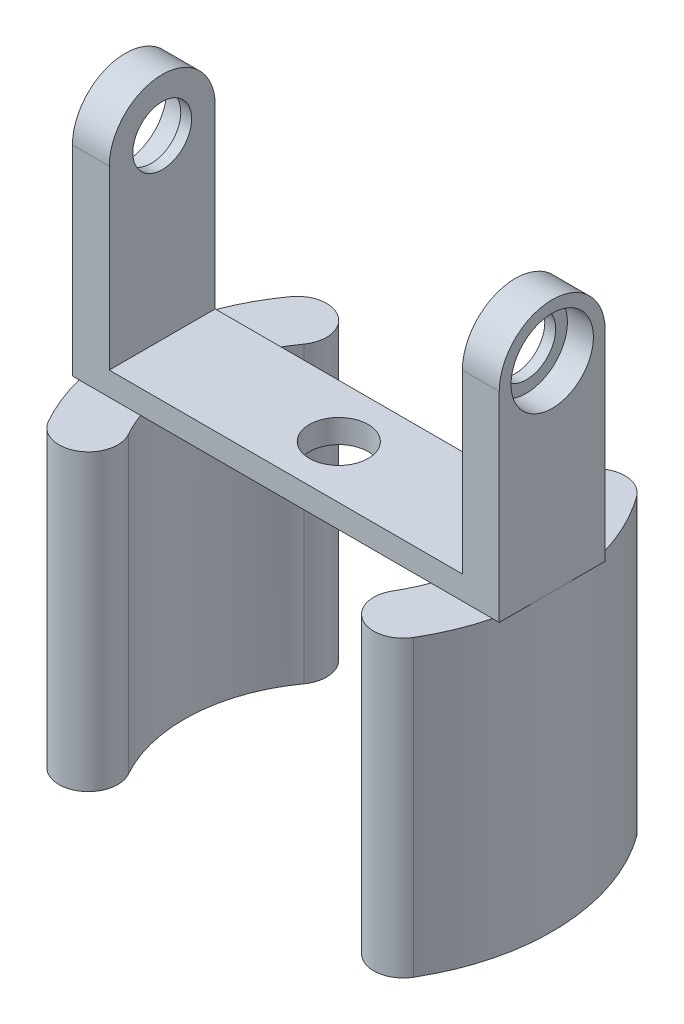
SolidWorks part; units mm, degrees
ref_plane "Front" through (0, 0, 0) normal (0, 0, 1) x (1, 0, 0)
ref_plane "Top" through (0, 0, 0) normal (0, 1, 0) x (1, 0, 0)
ref_plane "Right" through (0, 0, 0) normal (1, 0, 0) x (0, 0, -1)
sketch "Sketch1" plane through (0, 0, 0) normal (1, 0, 0) x (0, 0, -1)
  circle A0 centre (0, 0) radius 9
  circle A1 centre (0, 0) radius 5
  dimension "D1" = 10
  dimension "D2" = 18
extrude "Boss-Extrude1" add sketch "Sketch1" along normal blind 6.26
sketch "Sketch3" plane through (0, 0, 0) normal (-1, 0, 0) x (0, 0, 1)
  line L0 (-9, 0) -> (-9, -30)
  line L1 (-9, -30) -> (9, -30)
  line L2 (9, -30) -> (9, 0)
  line L3 (-9, 0) -> (9, 0) construction
  line L5 (-9, 0) -> (-5, 0)
  line L6 (5, 0) -> (9, 0)
  circle A0 centre (0, 0) radius 9 construction
  arc A1 (-5, 0) -> (5, 0) centre (0, 0) ccw
  circle A2 centre (0, 0) radius 5 construction
  point P10 (-9, 0)
  dimension "D1" = 30
extrude "Boss-Extrude2" add sketch "Sketch3" against normal up to surface (6.26 mm away) up to face at (6.26, 0, -9)
sketch "Sketch2" plane through (6.26, 0, 0) normal (1, 0, 0) x (0, 0, -1)
  circle A0 centre (0, 0) radius 7
  dimension "D1" = 14
extrude "Cut-Extrude1" cut sketch "Sketch2" against normal blind 4.41
sketch "Sketch4" plane through (0, -30, 0) normal (0, -1, 0) x (1, 0, 0)
  line L0 (6.26, -9) -> (6.26, 9) construction
  line L1 (6.26, 9) -> (-30, 9)
  line L2 (6.26, 9) -> (6.26, -9)
  line L3 (6.26, -9) -> (-30, -9)
  line L4 (-30, 9) -> (-30, -9)
  point P6 (6.26, 0)
  point P7 (6.26, 0)
  dimension "D1" = 36.26
  dimension "D2" = 18
extrude "Boss-Extrude3" add sketch "Sketch4" along normal blind 4
ref_plane "Plane1" through (-30, 0, 0) normal (-1, 0, 0) x (0, 0, 1)
mirror "Mirror2" about plane through (-30, -34, 9) normal (1, 0, 0) of bodies 104
sketch "Sketch5" plane through (0, -30, 0) normal (0, 1, 0) x (1, 0, 0)
  line L0 (-60, 9) -> (0, 9) construction
  line L1 (-30, 9) -> (-30, -9) construction
  line L2 (0, -9) -> (-60, -9) construction
  circle A0 centre (-30, 0) radius 5
  point P0 (-30, 9)
  dimension "D1" = 10
extrude "Cut-Extrude2" cut sketch "Sketch5" against normal through all
sketch "Sketch6" plane through (0, -34, 0) normal (0, -1, 0) x (1, 0, 0)
  line L0 (-0.5857, -21.2035) -> (-59.4143, -21.2035) construction
  line L1 (1.1847, 18.5014) -> (-61.6387, 17.7139) construction
  line L2 (6.26, -9) -> (6.26, 9) construction
  arc A0 (1.1847, 18.5014) -> (-0.5857, -21.2035) centre (-30, 0) cw
  arc A1 (-61.6387, 17.7139) -> (-59.4143, -21.2035) centre (-30, 0) ccw
  arc A2 (-7.4156, 13.399) -> (-8.6978, -15.3558) centre (-30, 0) cw
  arc A3 (1.1847, 18.5014) -> (-7.4156, 13.399) centre (-3.1154, 15.9502) ccw
  arc A4 (-0.5857, -21.2035) -> (-8.6978, -15.3558) centre (-4.6417, -18.2796) cw
  arc A5 (-52.9132, 12.8287) -> (-51.3022, -15.3558) centre (-30, 0) ccw
  arc A6 (-61.6387, 17.7139) -> (-52.9132, 12.8287) centre (-57.2759, 15.2713) cw
  arc A7 (-59.4143, -21.2035) -> (-51.3022, -15.3558) centre (-55.3583, -18.2796) ccw
  dimension "D1" = 10
  dimension "D2" = 10
extrude "Boss-Extrude4" add sketch "Sketch6" along normal blind 50
